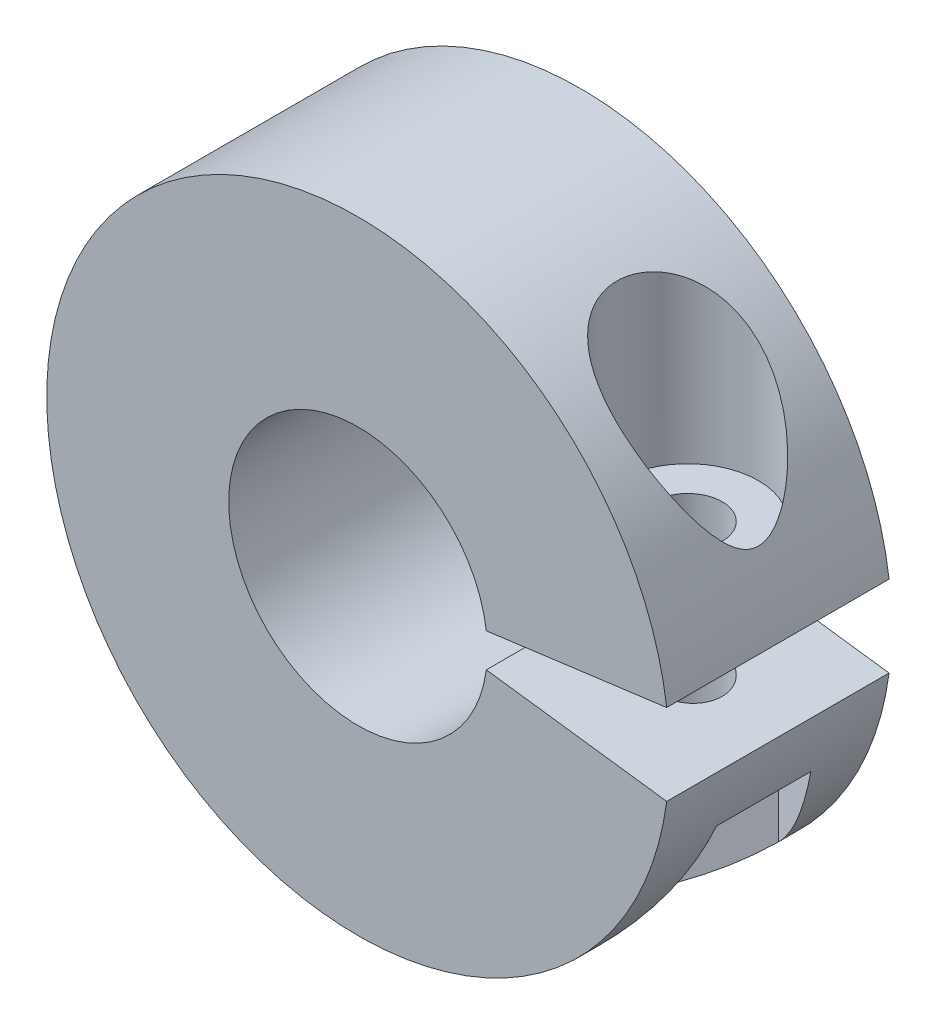
SolidWorks part; units mm, degrees
ref_plane "Front Plane" through (0, 0, 0) normal (0, 0, 1) x (1, 0, 0)
ref_plane "Top Plane" through (0, 0, 0) normal (0, 1, 0) x (1, 0, 0)
ref_plane "Right Plane" through (0, 0, 0) normal (1, 0, 0) x (0, 0, -1)
sketch "Sketch1" plane through (0, 0, 0) normal (0, 0, 1) x (1, 0, 0)
  line L0 (6.3452, 0.8354) -> (15.2683, 2.0101)
  line L1 (6.3452, -0.8354) -> (15.2683, -2.0101)
  line L2 (0, 0) -> (13.4282, 0) construction
  arc A0 (6.3452, 0.8354) -> (6.3452, -0.8354) centre (0, 0) ccw
  arc A1 (15.2683, 2.0101) -> (15.2683, -2.0101) centre (0, 0) ccw
  dimension "D1" = 6.4
  dimension "D3" = 15
  dimension "D2" = 9
extrude "Boss-Extrude1" add sketch "Sketch1" along normal blind 11
sketch "Sketch3" plane through (0, 0, 0) normal (0, 1, 0) x (1, 0, 0)
  line L0 (15.2683, -5.5) -> (6.3452, -5.5) construction
  line L4 (10.8067, -1) -> (6.9096, -3.25)
  line L5 (6.9096, -3.25) -> (6.9096, -7.75)
  line L6 (6.9096, -7.75) -> (10.8067, -10)
  line L7 (15.2683, 0) -> (6.3452, 0)
  line L8 (15.2683, -11) -> (15.2683, 0)
  line L9 (6.3452, -11) -> (15.2683, -11)
  line L10 (6.3452, 0) -> (6.3452, -11)
  line L11 (15.2683, 0) -> (6.3452, 0) construction
  line L12 (15.2683, -11) -> (15.2683, 0) construction
  line L13 (6.3452, -11) -> (15.2683, -11) construction
  line L14 (6.3452, 0) -> (6.3452, -11) construction
  line L15 (10.8067, -10) -> (14.7039, -7.75)
  line L16 (14.7039, -7.75) -> (14.7039, -3.25)
  line L17 (14.7039, -3.25) -> (10.8067, -1)
  circle A0 centre (10.8067, -5.5) radius 3.5
  circle A1 centre (10.8067, -5.5) radius 1.7
  circle A2 centre (10.8067, -5.5) radius 3.8971 construction
  point P4 (10.8067, -5.5)
  point P6 (10.8067, -1)
  point P19 (0, 0)
  dimension "D1" = 3.4
  dimension "D2" = 7
  dimension "D4" = 4.5
  dimension "D3" = 0
extrude "Cut-Extrude1" cut sketch "Sketch3" against normal through all both and the other way through all contours A1 region at (10.8067, 0, 5.5)
extrude "Cut-Extrude2" cut sketch "Sketch3<3>" along normal through all from offset 5 contours A0 A1 region at (7.4057, 0, 5.5)
sketch "Sketch3<3>" plane through (0, 0, 0) normal (0, 1, 0) x (1, 0, 0) same geometry as "Sketch3"
extrude "Cut-Extrude3" cut sketch "Sketch3<5>" against normal through all from offset 5 contours L16 L17 L4 L5 L6 L15 A0 | A0 A1 region at (12.6958, 0, 2.2281) region at (7.4057, 0, 5.5) offset against normal yes
sketch "Sketch3<5>" plane through (0, 0, 0) normal (0, 1, 0) x (1, 0, 0) same geometry as "Sketch3"
